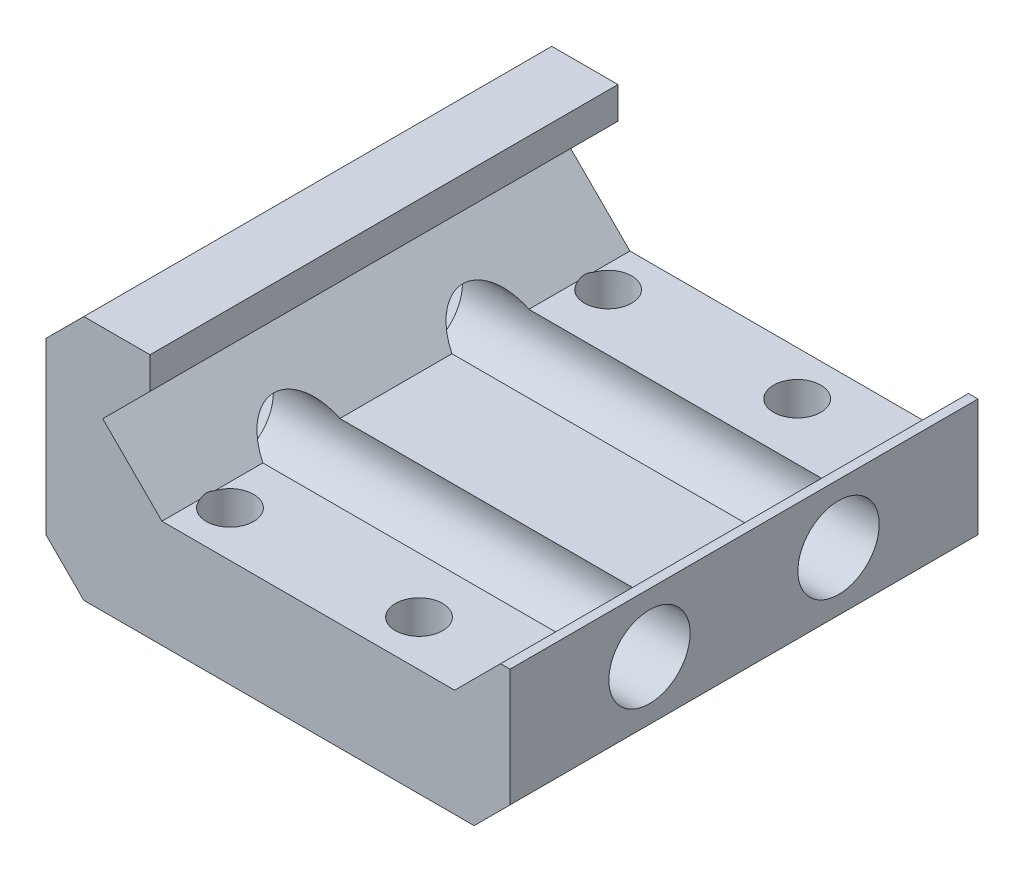
SolidWorks part; units mm, degrees
ref_plane "Płaszczyzna przednia" through (0, 0, 0) normal (0, 0, 1) x (1, 0, 0)
ref_plane "Płaszczyzna górna" through (0, 0, 0) normal (0, 1, 0) x (1, 0, 0)
ref_plane "Płaszczyzna prawa" through (0, 0, 0) normal (1, 0, 0) x (0, 0, -1)
sketch "Szkic1" plane through (0, 0, 0) normal (0, 0, 1) x (1, 0, 0)
  line L0 (-3, 4.18) -> (2.5, 4.18)
  line L2 (-3, -8.82) -> (-3, 4.18)
  line L5 (21.74, 0) -> (21.74, -7.02) construction
  line L6 (1.37, -1.37) -> (20.37, -1.37) construction
  line L7 (2.5, 4.18) -> (2.5, 2.5)
  line L8 (2.5, 2.5) -> (0, 0)
  line L9 (0, 0) -> (3.13, -3.13)
  line L10 (3.13, -3.13) -> (18.61, -3.13)
  line L11 (18.61, -3.13) -> (21.54, -0.2)
  line L14 (21.54, -0.2) -> (21.54, -6.92)
  line L17 (21.54, -6.92) -> (19.64, -8.82)
  line L18 (-3, -8.82) -> (19.64, -8.82)
  line L19 (1.37, -1.37) -> (1.37, 1.37) construction
  line L20 (1.37, 1.37) -> (20.37, 1.37) construction
  line L21 (20.37, -1.37) -> (20.37, 1.37) construction
  dimension "D1" = 45
  dimension "D2" = 45
  dimension "D3" = 5.5
  dimension "D4" = 1.68
  dimension "D5" = 13
  dimension "D6" = 0.3
  dimension "D7" = 19
  dimension "D8" = 2.74
  dimension "D9" = 4.5
  dimension "D10" = 3
  dimension "D11" = 0.2
extrude "Dodanie-wyciągnięcie3" add sketch "Szkic1" along normal blind 24.75
sketch "Szkic3" plane through (21.54, 0, 0) normal (1, 0, 0) x (0, 0, -1)
  line L1 (-7.375, -3.82) -> (-17.375, -3.82) construction
  line L2 (-24.75, 0) -> (0, 0) construction
  line L3 (-24.75, -6.92) -> (0, -6.92) construction
  line L4 (-24.75, -6.92) -> (0, -6.92) construction
  line L5 (-12.375, -6.92) -> (-12.375, -3.82) construction
  circle A0 centre (-17.375, -3.82) radius 2.15
  circle A1 centre (-7.375, -3.82) radius 2.15
  dimension "D1" = 10
  dimension "D2" = 4.3
  dimension "D3" = 3.82
extrude "Wytnij-wyciągnięcie1" cut sketch "Szkic3" against normal through all
sketch "Szkic4" plane through (0, -3.13, 0) normal (0, 1, 0) x (1, 0, 0)
  line L0 (18.61, -24.75) -> (3.13, -24.75) construction
  circle A0 centre (0, -2.75) radius 2
  circle A1 centre (0, -22) radius 2
  dimension "D2" = 2.75
  dimension "D3" = 2.75
extrude "Wytnij-wyciągnięcie2" [suppressed] cut sketch "Szkic4" against normal blind 6
sketch "Szkic7" [suppressed] plane through (0, -3.13, 0) normal (0, 1, 0) x (1, 0, 0)
  circle A0 centre (0, -2.75) radius 2.5
  circle A1 centre (0, -22) radius 2.5
  dimension "D1" = 2.75
  dimension "D2" = 19.25
extrude "Wytnij-wyciągnięcie3" [suppressed] cut sketch "Szkic7" against normal blind 1.5
sketch "Sketch1" plane through (0, 0, 24.75) normal (0, 0, 1) x (1, 0, 0)
  line L0 (21.04, -0.7) -> (21.54, -0.7)
  line L1 (21.54, -0.2) -> (18.61, -3.13) construction
  line L2 (21.54, -6.92) -> (21.54, -0.2) construction
  line L13 (-3, -8.82) -> (19.64, -8.82)
  line L14 (19.64, -8.82) -> (21.54, -6.92)
  line L15 (21.54, -6.92) -> (21.54, -0.2)
  line L16 (21.54, -0.2) -> (18.61, -3.13)
  line L17 (18.61, -3.13) -> (3.13, -3.13)
  line L18 (3.13, -3.13) -> (0, 0)
  line L19 (0, 0) -> (2.5, 2.5)
  line L20 (2.5, 2.5) -> (2.5, 4.18)
  line L21 (2.5, 4.18) -> (-3, 4.18)
  line L22 (-3, 4.18) -> (-3, -8.82)
  line L25 (21.54, -0.7) -> (21.54, -0.2)
  line L26 (21.54, -0.2) -> (21.04, -0.7)
  dimension "D1" = 0.5
  dimension "D2" = 0
extrude "Cut-Extrude1" cut sketch "Sketch1" against normal through all
sketch "Sketch3" plane through (21.54, 0, 0) normal (1, 0, 0) x (0, 0, -1)
  circle A0 centre (-17.375, -3.82) radius 2.65
  circle A1 centre (-7.375, -3.82) radius 2.65
  dimension "D1" = 5.3
chamfer "Chamfer1" distance 2 angle 45 2 edges at (-3, 4.18, 12.375) (-3, -8.82, 12.375)
hole_wizard "Ø2.5 (2.5) Diameter Hole1" positions "Sketch4" profile "Sketch5" hole size "Ø2.5" standard "DIN" end condition through all
sketch "Sketch4" plane through (0, -8.82, 0) normal (0, -1, 0) x (-1, 0, 0)
  line L0 (-9.32, -19.9336) -> (-9.32, -24.75) construction
  line L4 (-4.32, -22.3418) -> (-9.32, -22.3418) construction
  line L6 (-9.32, 0) -> (-9.32, -4.8164) construction
  line L10 (-9.32, -2.3418) -> (-4.32, -2.3418) construction
  line L14 (1, -24.75) -> (-19.64, -24.75) construction
  point P0 (-4.32, -2.3418)
  point P4 (-14.32, -2.3418)
  point P5 (-14.32, -22.3418)
  point P6 (-4.32, -22.3418)
  dimension "D3" = 10
  dimension "D4" = 20
  dimension "D5" = 5
  dimension "D1" = 2
  dimension "D2" = 2
sketch "Sketch5" plane through (4.32, -8.82, 2.3418) normal (1, 0, 0) x (0, 0, -1)
  line L0 (0, 0) -> (0, 13)
  line L1 (0, 13) -> (1.25, 13)
  line L2 (1.25, 13) -> (1.25, 0)
  line L5 (1.25, 0) -> (0, 0)
  line L11 (0, -6.35) -> (0, 107.95) construction
  dimension "Thru Hole Dia." = 2.5
  dimension "Thru Hole Depth" = 13
sketch "Sketch6" plane through (-3, 0, 0) normal (-1, 0, 0) x (0, 0, 1)
  line L1 (9.3669, -7.27) -> (11.3587, -3.82)
  line L2 (11.3587, -3.82) -> (9.3669, -0.37)
  line L3 (9.3669, -0.37) -> (5.3831, -0.37)
  line L4 (5.3831, -0.37) -> (3.3913, -3.82)
  line L5 (3.3913, -3.82) -> (5.3831, -7.27)
  line L6 (5.3831, -7.27) -> (9.3669, -7.27)
  line L7 (15.3831, -7.27) -> (19.3669, -7.27)
  line L8 (19.3669, -7.27) -> (21.3587, -3.82)
  line L9 (21.3587, -3.82) -> (19.3669, -0.37)
  line L10 (19.3669, -0.37) -> (15.3831, -0.37)
  line L11 (15.3831, -0.37) -> (13.3913, -3.82)
  line L12 (13.3913, -3.82) -> (15.3831, -7.27)
  circle A0 centre (7.375, -3.82) radius 3.45 construction
  circle A1 centre (17.375, -3.82) radius 3.45 construction
  dimension "D1" = 6.9
extrude "Cut-Extrude2" cut sketch "Sketch6" against normal blind 2.5
